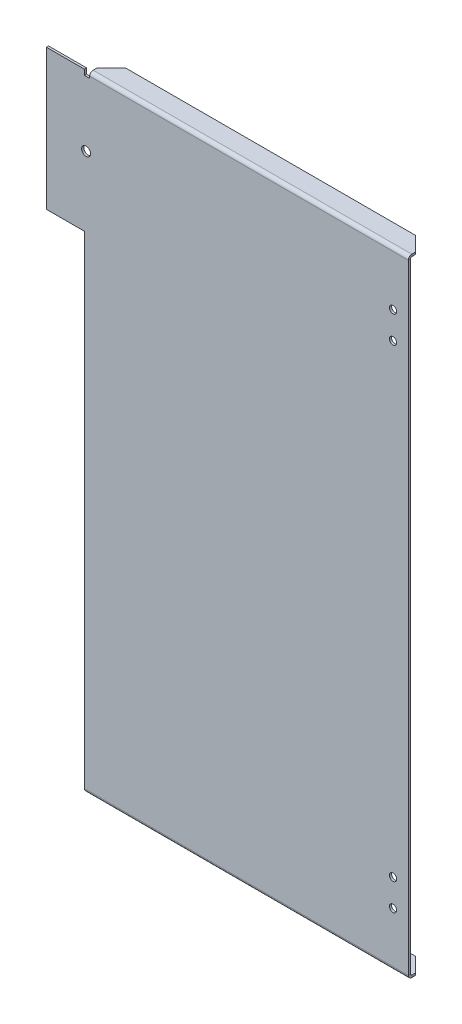
SolidWorks part; units mm, degrees
note: The reader was unsure of these and kept them because the rebuilt part matched: flange length of "Ребро-кромка1".
ref_plane "Спереди" through (0, 0, 0) normal (0, 0, 1) x (1, 0, 0)
ref_plane "Сверху" through (0, 0, 0) normal (0, 1, 0) x (1, 0, 0)
ref_plane "Справа" through (0, 0, 0) normal (1, 0, 0) x (0, 0, -1)
sketch "Эскиз1" plane through (0, 0, 0) normal (0, 0, 1) x (1, 0, 0)
  line L0 (0, 270) -> (-21, 270)
  line L1 (0, 0) -> (180, 0)
  line L2 (0, 0) -> (0, 270)
  line L3 (-21, 348) -> (180, 348)
  line L4 (180, 0) -> (180, 348)
  line L5 (-21, 270) -> (-21, 348)
  dimension "D1" = 348
  dimension "D2" = 180
  dimension "D3" = 201
  dimension "D4" = 78
base flange "Базовая кромка1" sketch "Эскиз1" thickness 1.2 reverse thickness direction no parameters "D1"=0.7366
sketch "Эскиз6" plane through (0, 0, 0) normal (0, 0, 1) x (1, 0, 0)
  line L0 (1, 348) -> (1, 270) construction
  line L1 (-21, 348) -> (180, 348) construction
  line L2 (-21, 270) -> (0, 270) construction
  line L3 (-21, 348) -> (-21, 270) construction
  circle A0 centre (1, 309) radius 2.5
  dimension "D2" = 5
  dimension "D1" = 22
extrude "Вырез-Вытянуть1" cut sketch "Эскиз6" against normal blind 10 normal cut yes
sketch "Эскиз7" plane through (0, 0, 0) normal (0, 0, 1) x (1, 0, 0)
  line L0 (171.5, 348) -> (171.5, 0) construction
  line L1 (180, 348) -> (-21, 348) construction
  line L2 (0, 0) -> (180, 0) construction
  line L3 (180, 0) -> (180, 348) construction
  circle A0 centre (171.5, 318) radius 2
  circle A1 centre (171.5, 303) radius 2
  circle A2 centre (171.5, 45) radius 2
  circle A3 centre (171.5, 30) radius 2
  dimension "D1" = 8.5
  dimension "D2" = 15
  dimension "D3" = 15
  dimension "D4" = 30
  dimension "D5" = 30
  dimension "D6" = 4
extrude "Вырез-Вытянуть2" cut sketch "Эскиз7" against normal blind 10 normal cut yes
sketch "Эскиз8" plane through (0, 0, 0) normal (0, 0, 1) x (1, 0, 0)
  line L0 (180, 348) -> (-21, 348) construction
  line L1 (0, 348) -> (3, 348)
  line L2 (0, 348) -> (0, 345)
  line L3 (0, 345) -> (3, 345)
  line L4 (3, 348) -> (3, 345)
  line L5 (0, 345) -> (0, 270) construction
  dimension "D1" = 3
  dimension "D2" = 3
extrude "Вырез-Вытянуть3" cut sketch "Эскиз8" against normal blind 10 normal cut yes
edge flange "Ребро-кромка1" sketch "Эскиз13" flange profiles "Эскиз13", "Эскиз14" flange angle 90 flange length 12 flange position material inside bend radius 0.7366 thickness 1.2 relief rectangular parameters "D6"=10, "D8"=1
sketch "Эскиз13" plane through (0, 348, -1.2) normal (0, 1, 0) x (1, 0, 0)
  line L2 (3, 0) -> (3, 10.8)
  line L3 (3, 10.8) -> (180, 10.8)
  line L4 (180, 10.8) -> (180, 0)
  line L5 (180, 0) -> (3, 0) construction
  line L6 (180, 0) -> (3, 0)
sketch "Эскиз14" plane through (0, 0, -1.2) normal (0, -1, 0) x (-1, 0, 0)
  line L0 (0, 0) -> (-180, 0) construction
  line L1 (0, 0) -> (-180, 0)
  line L2 (-180, 0) -> (-180, 10.8)
  line L3 (-180, 10.8) -> (0, 10.8)
  line L4 (0, 10.8) -> (0, 0)
bend "EdgeBend1" bend radius 0.7366 bend angle 90 parameters "D5"=1
bend "EdgeBend2" bend radius 0.7366 bend angle 90 parameters "D5"=2
chamfer "Фаска1" distance 8 angle 45 4 edges at (0, 0.6, -12) (180, 0.6, -12) (180, 347.4, -12) (3, 347.4, -12)
sketch "Сгиб-Линии1" plane through (0, 0, 0) normal (0, 1, 0) x (1, 0, 0)
sketch "Граничная рамка1" plane through (0, 0, 0) normal (0, 1, 0) x (1, 0, 0)
sheet metal parameters "Листовой металл3" thickness 1.2 parameters "D1"=0.7366
flat pattern "Развертка3" [suppressed]
sketch "Сгиб-Линии2" plane through (0, 0, 0) normal (0, 1, 0) x (1, 0, 0)
sketch "Граничная рамка2" [suppressed] plane through (0, 0, 0) normal (0, 1, 0) x (1, 0, 0)
sheet metal parameters "Листовой металл4" thickness 1.2 parameters "D1"=0.7366
flat pattern "Развертка3"
sketch "Сгиб-Линии2" plane through (0, 0, 0) normal (0, 1, 0) x (1, 0, 0)
sketch "Граничная рамка2" [suppressed] plane through (0, 0, 0) normal (0, 1, 0) x (1, 0, 0)
sheet metal parameters "Листовой металл5" thickness 1.2 parameters "D1"=0.7366
flat pattern "Развертка3"
sketch "Сгиб-Линии2" plane through (0, 0, 0) normal (0, 1, 0) x (1, 0, 0)
sketch "Граничная рамка2" [suppressed] plane through (0, 0, 0) normal (0, 1, 0) x (1, 0, 0)
sheet metal parameters "Листовой металл6" thickness 1.2 parameters "D1"=0.7366
flat pattern "Развертка3"
sketch "Сгиб-Линии2" plane through (0, 0, 0) normal (0, 1, 0) x (1, 0, 0)
sketch "Граничная рамка2" [suppressed] plane through (0, 0, 0) normal (0, 1, 0) x (1, 0, 0)
sheet metal parameters "Листовой металл7" thickness 1.2 parameters "D1"=0.7366
flat pattern "Развертка3" [suppressed]
sketch "Сгиб-Линии2" plane through (0, 0, 0) normal (0, 1, 0) x (1, 0, 0)
sketch "Граничная рамка2" [suppressed] plane through (0, 0, 0) normal (0, 1, 0) x (1, 0, 0)
bend of the flat pattern "Плоское состояние-<EdgeBend1>1"
bend of the flat pattern "Плоское состояние-<EdgeBend2>1"
